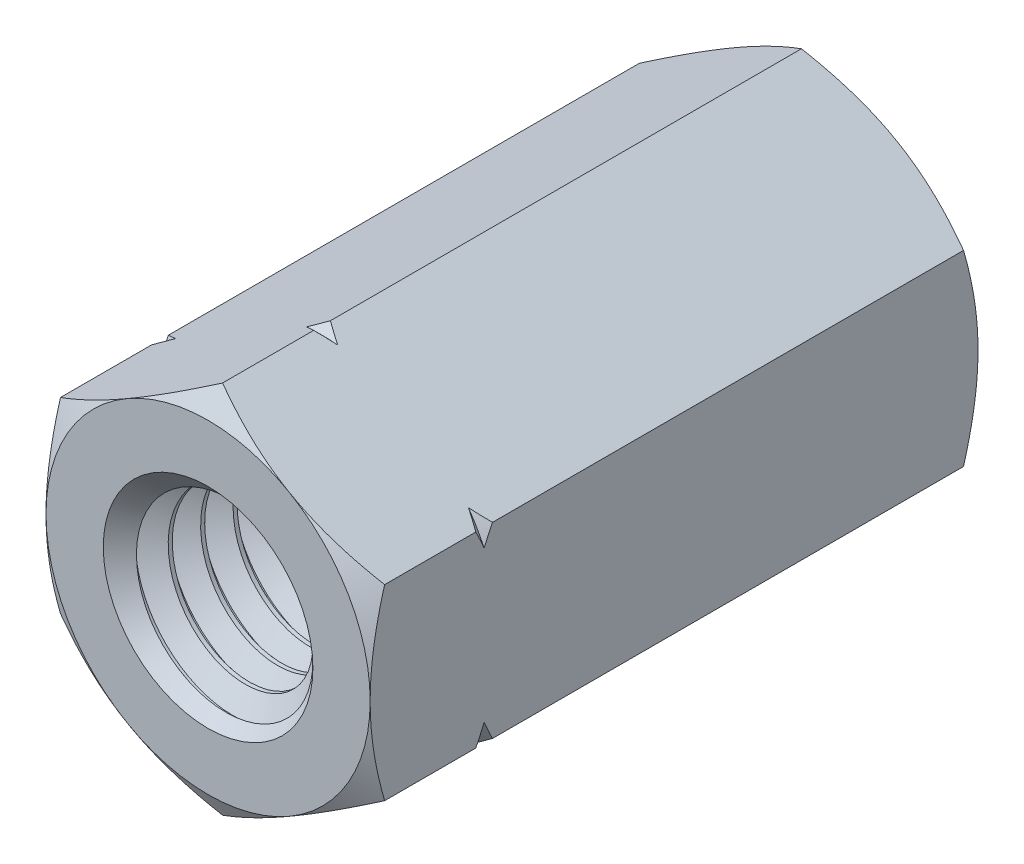
SolidWorks part; units mm, degrees
ref_plane "Front Plane" through (0, 0, 0) normal (0, 0, 1) x (1, 0, 0)
ref_plane "Top Plane" through (0, 0, 0) normal (0, 1, 0) x (1, 0, 0)
ref_plane "Right Plane" through (0, 0, 0) normal (1, 0, 0) x (0, 0, -1)
sketch "Sketch1" plane through (0, 0, 0) normal (1, 0, 0) x (0, 0, -1)
  line L0 (0, -4) -> (0, 4) construction
  line L1 (0, 0) -> (15, 0) construction
  line L2 (0, -2.5) -> (0, 2.5) construction
  line L3 (-0.75, 2.5866) -> (0.05, 2.5866) construction
  line L4 (0.05, 2.5866) -> (-0.35, 1.8938) construction
  line L5 (-0.35, 1.8938) -> (-0.75, 2.5866) construction
  line L6 (-0.725, 2.5433) -> (0.025, 2.5433) construction
  line L7 (-0.7, 2.5) -> (0, 2.5) construction
  line L8 (-0.4, 1.9804) -> (-0.3, 1.9804) construction
  line L9 (-0.35, 1.9804) -> (-0.35, 1.8938) construction
  line L10 (-0.35, 2.5) -> (-0.35, 2.5866) construction
  point P4 (0, 0)
  point P10 (0, 0)
  point P12 (0, -2.5)
  point P23 (-0.35, 2.5433)
  dimension "Hex" = 8
  dimension "Length" = 15
  dimension "Thread OD" = 5
  dimension "D1" = 60
  dimension "Pitch" = 0.8
sketch "Sketch2" plane through (0, 0, 0) normal (0, 0, 1) x (1, 0, 0)
  line L1 (-4, 2.3094) -> (-4, -2.3094)
  line L2 (-4, -2.3094) -> (0, -4.6188)
  line L3 (0, -4.6188) -> (4, -2.3094)
  line L4 (4, -2.3094) -> (4, 2.3094)
  line L5 (4, 2.3094) -> (0, 4.6188)
  line L6 (0, 4.6188) -> (-4, 2.3094)
  circle A0 centre (0, 0) radius 4 construction
  circle A1 centre (0, 0) radius 2.5
extrude "Boss-Extrude1" add sketch "Sketch2" against normal up to vertex (15 mm away) up to point (0, 0, -15)
sketch "Sketch3" plane through (0, 0, 0) normal (0, 0, 1) x (1, 0, 0)
  circle A0 centre (0, 0) radius 4 construction
  circle A1 centre (0, 0) radius 4
extrude "Cut-Extrude2" cut sketch "Sketch3" against normal through all draft 60 flip side to cut
sketch "Sketch4" plane through (0, 0, -15) normal (0, 0, -1) x (-1, 0, 0)
  circle A0 centre (0, 0) radius 4 construction
  circle A1 centre (0, 0) radius 4
extrude "Cut-Extrude3" cut sketch "Sketch4" against normal through all draft 60 flip side to cut
sketch "Sketch9" plane through (0, 0, 0) normal (1, 0, 0) x (0, 0, -1)
  line L0 (2.6062, 4.6188) -> (3.0188, 4.6188)
  line L1 (14.6427, 4.6188) -> (0.3573, 4.6188) construction
  line L2 (3.0188, 4.6188) -> (2.8125, 4.4125)
  line L3 (2.8125, 4.4125) -> (2.6062, 4.6188)
  line L4 (0, 4) -> (2.8125, 4) construction
  line L5 (2.8125, 4) -> (2.8125, 4.2063) construction
  line L6 (0, -4) -> (0, 4) construction
  line L7 (2.8125, 4.2063) -> (2.8125, 4.4125) construction
  line L8 (2.8125, 4.4125) -> (2.8125, 4.6188) construction
  dimension "D1" = 2.8125
  dimension "D2" = 90
revolve "Cut-Revolve1" cut sketch "Sketch9" angle 360 about L1
sketch "Sketch5" plane through (0, 0, 0) normal (0, 0, 1) x (1, 0, 0)
  circle A0 centre (0, 0) radius 2.5 construction
  circle A1 centre (0, 0) radius 2.5
ref_axis "Center Axis 1" through (0, 0, -64.1198) along (0, 0, 1)
curve "Helix/Spiral1" pitch 0.8 height 15.8 radius 2.5 centre (0, 0, 0) axis (0, 0, -1) start towards (0, 1, 0)
sketch "Sketch6" plane through (0, 0, 0) normal (1, 0, 0) x (0, 0, -1)
  line L0 (-0.725, 2.5433) -> (0.025, 2.5433)
  line L1 (0.025, 2.5433) -> (-0.3, 1.9804)
  line L2 (-0.3, 1.9804) -> (-0.4, 1.9804)
  line L3 (-0.4, 1.9804) -> (-0.725, 2.5433)
sweep "Sweep1" add profiles "Sketch6" path "Helix/Spiral1"
sketch "Sketch7" plane through (0, 0, 0) normal (0, 0, 1) x (1, 0, 0)
  circle A0 centre (0, 0) radius 2.5866
extrude "Cut-Extrude4" cut sketch "Sketch7" along normal through all and the other way through all draft 45
sketch "Sketch8" plane through (0, 0, -15) normal (0, 0, -1) x (-1, 0, 0)
  circle A0 centre (0, 0) radius 2.5866
extrude "Cut-Extrude5" cut sketch "Sketch8" along normal through all and the other way through all draft 45
equation "\"D2@Sketch1\"=\"Pitch@Sketch1\"/8"
equation "\"D4@Helix/Spiral1\"=\"Pitch@Sketch1\""
equation "\"D3@Helix/Spiral1\"=\"Length@Sketch1\"+\"Pitch@Sketch1\""
equation "\"D1@Sketch9\"=\"Length@Sketch1\"*.1875"
